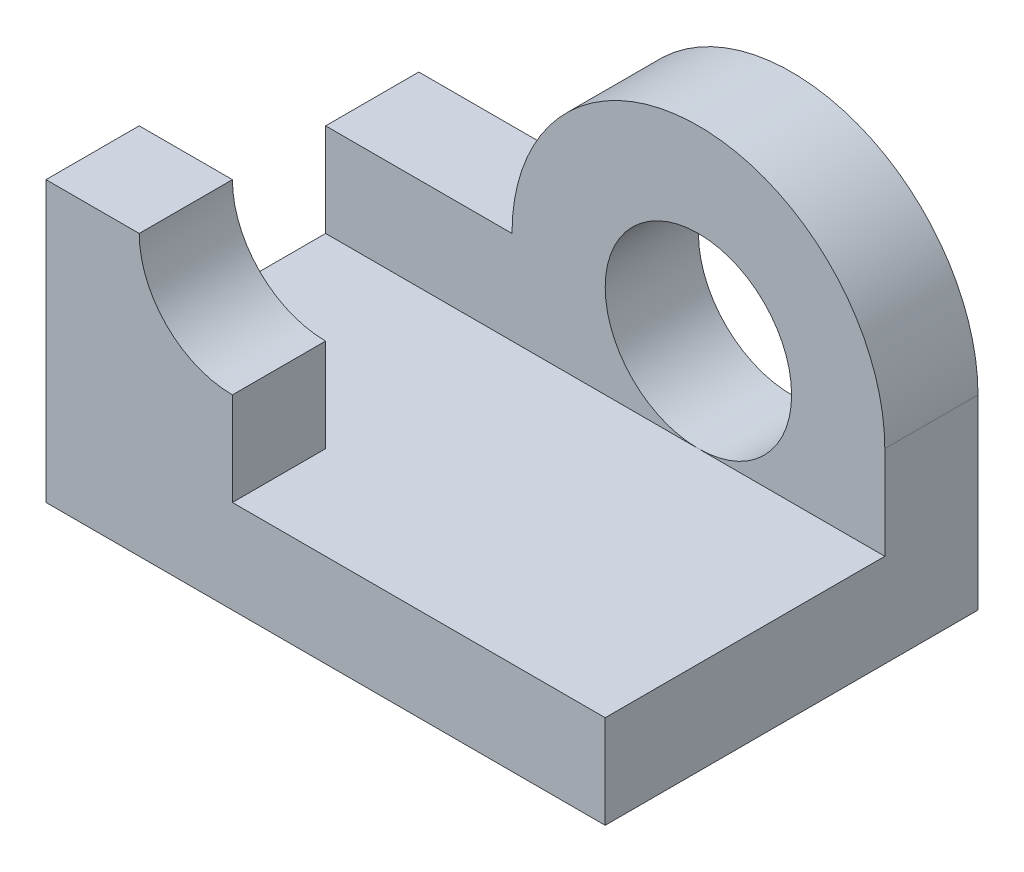
SolidWorks part; units mm, degrees
ref_plane "Front Plane" through (0, 0, 0) normal (0, 0, 1) x (1, 0, 0)
ref_plane "Top Plane" through (0, 0, 0) normal (0, 1, 0) x (1, 0, 0)
ref_plane "Right Plane" through (0, 0, 0) normal (1, 0, 0) x (0, 0, -1)
sketch "Sketch1" plane through (0, 0, 0) normal (0, 1, 0) x (1, 0, 0)
  line L1 (0, 0) -> (60, 0)
  line L2 (0, 0) -> (0, 40)
  line L3 (0, 40) -> (60, 40)
  line L4 (60, 0) -> (60, 40)
  dimension "D1" = 60
  dimension "D2" = 40
extrude "Boss-Extrude1" add sketch "Sketch1" along normal blind 10
sketch "Sketch2" plane through (0, 0, 0) normal (0, 0, 1) x (1, 0, 0)
  line L0 (0, 10) -> (0, 30)
  line L1 (0, 30) -> (10, 30)
  line L2 (10, 30) -> (10, 20)
  line L3 (10, 20) -> (20, 20)
  line L4 (20, 20) -> (20, 10)
  line L5 (0, 10) -> (60, 10) construction
  line L6 (20, 10) -> (0, 10)
  dimension "D1" = 20
  dimension "D2" = 20
  dimension "D3" = 10
  dimension "D4" = 10
extrude "Boss-Extrude2" add sketch "Sketch2" against normal blind 10
sketch "Sketch3" plane through (0, 0, -40) normal (0, 0, -1) x (-1, 0, 0)
  line L0 (0, 0) -> (-60, 0)
  line L1 (-60, 0) -> (-60, 20)
  line L2 (-20, 20) -> (0, 20)
  line L3 (0, 30) -> (0, 10) construction
  line L4 (0, 20) -> (0, 0)
  arc A0 (-60, 20) -> (-20, 20) centre (-40, 20) cw
  circle A1 centre (-40, 20) radius 10
  dimension "D2" = 20
  dimension "D3" = 20
  dimension "D1" = 20
extrude "Boss-Extrude3" add sketch "Sketch3" against normal blind 10
fillet "Fillet1" radius 10 1 edges at (10, 20, -5)
